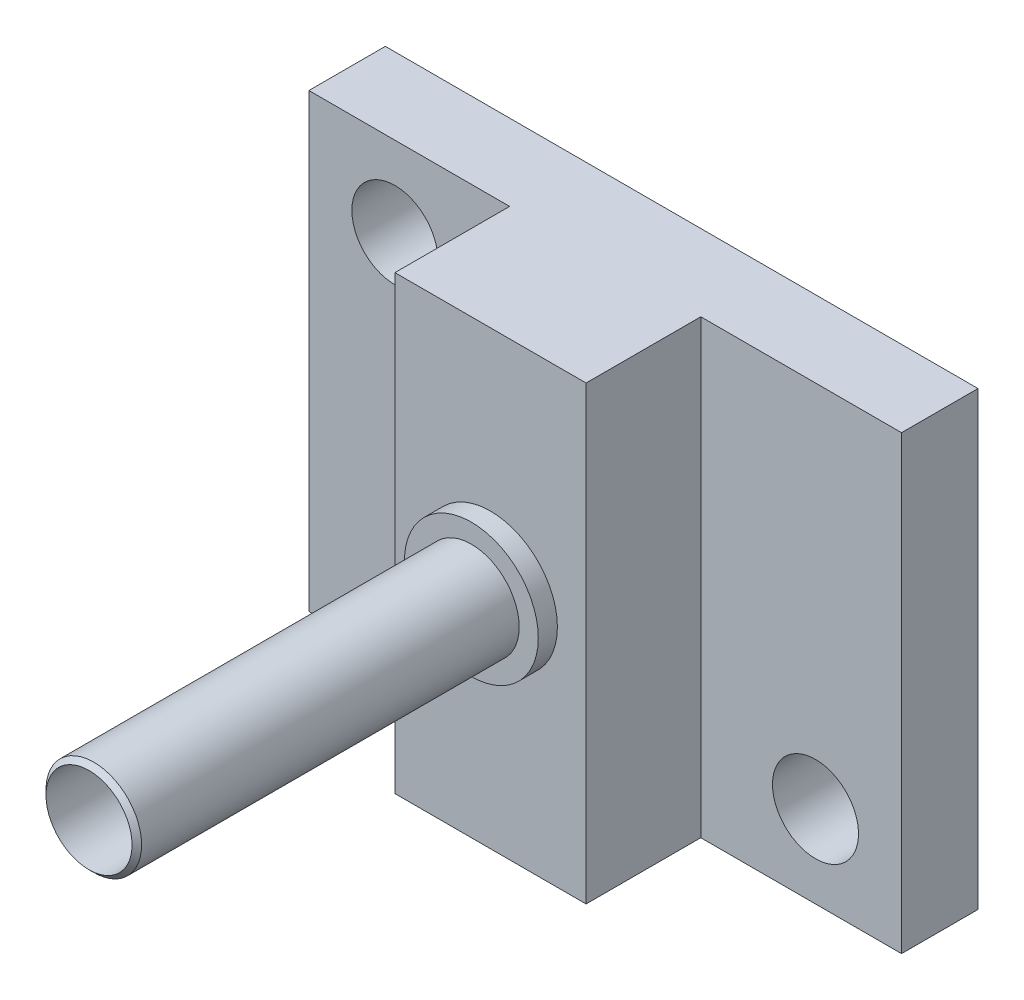
SolidWorks part; units mm, degrees
ref_plane "Front Plane" through (0, 0, 0) normal (0, 0, 1) x (1, 0, 0)
ref_plane "Top Plane" through (0, 0, 0) normal (0, 1, 0) x (1, 0, 0)
ref_plane "Right Plane" through (0, 0, 0) normal (1, 0, 0) x (0, 0, -1)
sketch "Sketch1" plane through (0, 0, 0) normal (0, 0, 1) x (1, 0, 0)
  circle A0 centre (15.5, 11.8) radius 8.5
extrude "Boss-Extrude1" add sketch "Sketch1" along normal blind 1
sketch "Sketch2" plane through (0, 0, 1) normal (0, 0, 1) x (1, 0, 0)
  line L1 (0, 0) -> (31, 0)
  line L2 (0, 0) -> (0, 23.6)
  line L3 (0, 23.6) -> (31, 23.6)
  line L4 (31, 0) -> (31, 23.6)
  line L5 (0, 0) -> (31, 23.6) construction
  line L6 (0, 23.6) -> (31, 0) construction
  point P4 (15.5, 11.8)
extrude "Boss-Extrude2" add sketch "Sketch2" along normal blind 4
sketch "Sketch3" plane through (0, 0, 5) normal (0, 0, 1) x (1, 0, 0)
  line L1 (10.5, 0) -> (20.5, 0)
  line L2 (10.5, 0) -> (10.5, 23.6)
  line L3 (10.5, 23.6) -> (20.5, 23.6)
  line L4 (20.5, 0) -> (20.5, 23.6)
  line L5 (10.5, 0) -> (20.5, 23.6) construction
  line L6 (10.5, 23.6) -> (20.5, 0) construction
  point P4 (15.5, 11.8)
extrude "Boss-Extrude3" add sketch "Sketch3" along normal blind 6
sketch "Sketch4" plane through (0, 0, 11) normal (0, 0, 1) x (1, 0, 0)
  circle A0 centre (15.5, 11.8) radius 3.5
extrude "Boss-Extrude4" add sketch "Sketch4" along normal blind 1
sketch "Sketch5" plane through (0, 0, 12) normal (0, 0, 1) x (1, 0, 0)
  circle A0 centre (15.5, 11.8) radius 2.5
extrude "Boss-Extrude5" add sketch "Sketch5" along normal blind 20.25
sketch "Sketch7" plane through (0, 0, 32.25) normal (0, 0, 1) x (1, 0, 0)
  circle A0 centre (15.5, 11.8) radius 2.25
extrude "Cut-Extrude1" cut sketch "Sketch7" against normal blind 12
sketch "Sketch8" plane through (0, 0, 1) normal (0, 0, -1) x (-1, 0, 0)
  circle A0 centre (-26.5, 4.3) radius 2.25
  circle A1 centre (-4.5, 19.3) radius 2.25
extrude "Cut-Extrude2" cut sketch "Sketch8" against normal through all
chamfer "Chamfer1" distance 0.5 angle 45 1 edges at (18, 11.8, 32.25)
